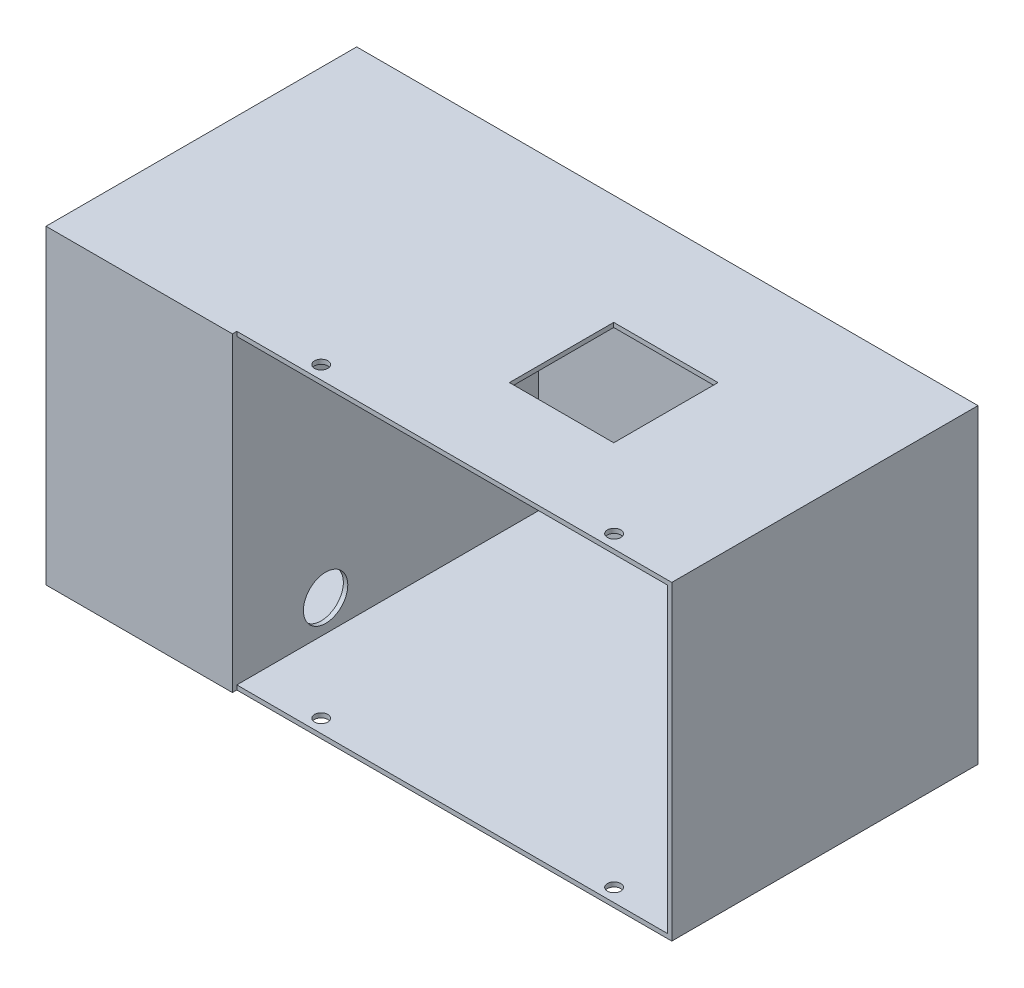
SolidWorks part; units mm, degrees
ref_plane "Спереди" through (0, 0, 0) normal (0, 0, 1) x (1, 0, 0)
ref_plane "Сверху" through (0, 0, 0) normal (0, 1, 0) x (1, 0, 0)
ref_plane "Справа" through (0, 0, 0) normal (1, 0, 0) x (0, 0, -1)
sketch "Эскиз1" plane through (0, 0, 0) normal (0, 0, 1) x (1, 0, 0)
  line L1 (-54.5294, 39.3927) -> (85.4706, 39.3927)
  line L2 (-54.5294, 39.3927) -> (-54.5294, -30.6073)
  line L3 (-54.5294, -30.6073) -> (85.4706, -30.6073)
  line L4 (85.4706, 39.3927) -> (85.4706, -30.6073)
  line L5 (-54.5294, 39.3927) -> (85.4706, 39.3927)
  line L6 (-54.5294, 39.3927) -> (-54.5294, -30.6073)
  line L7 (-54.5294, -30.6073) -> (85.4706, -30.6073)
  line L8 (85.4706, 39.3927) -> (85.4706, -30.6073)
extrude "Вытянуть-Тонкостенный1" add sketch "Эскиз1" along normal blind 70 thin contours L2 L1 L4 L3 thin type one direction reverse wall 1
extrude "Бобышка-Вытянуть1" add sketch "Эскиз1<3>" along normal blind 1 contours L4 L1 L2 L3 region at (15.4706, 4.3927, 0)
sketch "Эскиз1<3>" plane through (0, 0, 0) normal (0, 0, 1) x (1, 0, 0) same geometry as "Эскиз1"
sketch "草图2" plane through (0, 0, 1) normal (0, 0, 1) x (1, 0, 0)
  line L0 (-53.5294, 38.3927) -> (84.4706, 38.3927) construction
  line L1 (-13.5294, 38.3927) -> (-12.5294, 38.3927)
  line L2 (-13.5294, 38.3927) -> (-13.5294, -29.6073)
  line L3 (-13.5294, -29.6073) -> (-12.5294, -29.6073)
  line L4 (-12.5294, 38.3927) -> (-12.5294, -29.6073)
  line L5 (-53.5294, -29.6073) -> (84.4706, -29.6073) construction
  line L6 (-53.5294, 38.3927) -> (-53.5294, -29.6073) construction
  dimension "D1" = 1
  dimension "D2" = 40
extrude "凸台-拉伸1" add sketch "草图2" along normal blind 68
sketch "草图3" plane through (-54.5294, 0, 0) normal (-1, 0, 0) x (0, 0, 1)
  line L0 (0, 39.3927) -> (0, -30.6073) construction
  line L1 (1, 38.3927) -> (69, 38.3927)
  line L2 (1, 38.3927) -> (1, -29.6073)
  line L3 (1, -29.6073) -> (69, -29.6073)
  line L4 (69, 38.3927) -> (69, -29.6073)
  line L5 (70, 39.3927) -> (0, 39.3927) construction
  line L6 (70, -30.6073) -> (0, -30.6073) construction
  line L7 (70, 39.3927) -> (70, -30.6073) construction
  dimension "D1" = 1
  dimension "D2" = 1
  dimension "D3" = 1
  dimension "D4" = 1
extrude "切除-拉伸1" cut sketch "草图3" against normal blind 25
sketch "草图4" plane through (-54.5294, 0, 0) normal (-1, 0, 0) x (0, 0, 1)
  line L0 (70, -30.6073) -> (0, -30.6073) construction
  line L1 (70, 39.3927) -> (69, 39.3927)
  line L2 (70, 39.3927) -> (70, -30.6073)
  line L3 (70, -30.6073) -> (69, -30.6073)
  line L4 (69, 39.3927) -> (69, -30.6073)
  line L5 (69, -29.6073) -> (69, 38.3927) construction
extrude "凸台-拉伸2" add sketch "草图4" against normal blind 42
sketch "草图5" plane through (-13.5294, 0, 0) normal (-1, 0, 0) x (0, 0, 1)
  line L3 (69, 38.3927) -> (1, 38.3927) construction
  circle A0 centre (35, 14.3927) radius 5
  circle A1 centre (35, 14.3927) radius 3
  point P9 (35, 38.3927)
  dimension "D1" = 10
  dimension "D2" = 6
  dimension "D3" = 24
extrude "凸台-拉伸3" add sketch "草图5" along normal blind 20
sketch "草图6" plane through (-13.5294, 0, 0) normal (-1, 0, 0) x (0, 0, 1)
  line L0 (1, 38.3927) -> (1, -29.6073) construction
  line L1 (1, -13.6073) -> (69, -13.6073)
  line L2 (1, -13.6073) -> (1, -14.6073)
  line L3 (1, -14.6073) -> (69, -14.6073)
  line L4 (69, -13.6073) -> (69, -14.6073)
  line L5 (69, -29.6073) -> (69, 38.3927) construction
  line L6 (1, -29.6073) -> (69, -29.6073) construction
  dimension "D1" = 1
  dimension "D2" = 15
extrude "凸台-拉伸4" add sketch "草图6" along normal blind 41.5
sketch "草图8" plane through (0, 38.3927, 0) normal (0, -1, 0) x (1, 0, 0)
  line L0 (-12.5294, 70) -> (-12.5294, 1) construction
  line L1 (84.4706, 70) -> (84.4706, 1) construction
  line L2 (-54.5294, 70) -> (85.4706, 70) construction
  line L3 (-12.5294, 70) -> (84.4706, 70) construction
  circle A0 centre (3.4706, 66) radius 1.5
  circle A1 centre (69.4706, 66) radius 1.5
  dimension "D3" = 3
  dimension "D4" = 4
  dimension "D5" = 3
  dimension "D1" = 16
  dimension "D2" = 15
  dimension "D6" = 4
extrude "切除-拉伸2" cut sketch "草图8" against normal mid plane 200
sketch "草图10" plane through (0, 0, 70) normal (0, 0, 1) x (1, 0, 0)
  line L0 (-54.5294, -30.6073) -> (85.4706, -30.6073) construction
  line L5 (-12.5294, 39.3927) -> (85.4706, 39.3927)
  line L6 (-12.5294, 39.3927) -> (-12.5294, -30.6073)
  line L7 (-12.5294, -30.6073) -> (85.4706, -30.6073)
  line L8 (85.4706, 39.3927) -> (85.4706, -30.6073)
  line L10 (85.4706, 39.3927) -> (85.4706, -30.6073) construction
  dimension "D1" = 70
  dimension "D2" = 0
  dimension "D3" = 98
  dimension "D4" = 0
extrude "切除-拉伸5" cut sketch "草图10" against normal blind 1
sketch "草图11" plane through (0, -13.6073, 0) normal (0, 1, 0) x (1, 0, 0)
  circle A0 centre (-48.9389, -61.9228) radius 1.5
  dimension "D1" = 3
extrude "切除-拉伸6" cut sketch "草图11" against normal blind 1.5
sketch "草图12" plane through (0, 39.3927, 0) normal (0, 1, 0) x (1, 0, 0)
  line L1 (28.1884, -24.795) -> (51.6884, -24.795)
  line L2 (28.1884, -24.795) -> (28.1884, -48.295)
  line L3 (28.1884, -48.295) -> (51.6884, -48.295)
  line L4 (51.6884, -24.795) -> (51.6884, -48.295)
  dimension "D1" = 23.5
  dimension "D2" = 23.5
extrude "切除-拉伸7" cut sketch "草图12" against normal blind 28.5 contours L1 L4 L3 L2
sketch "草图13" plane through (-13.5294, 0, 0) normal (-1, 0, 0) x (0, 0, 1)
  line L0 (69, -29.6073) -> (69, -14.6073) construction
  line L1 (1, -14.6073) -> (69, -14.6073) construction
  circle A0 centre (49, -22.6073) radius 5
  dimension "D1" = 10
  dimension "D2" = 20
  dimension "D3" = 8
extrude "切除-拉伸8" cut sketch "草图13" against normal blind 16.5
